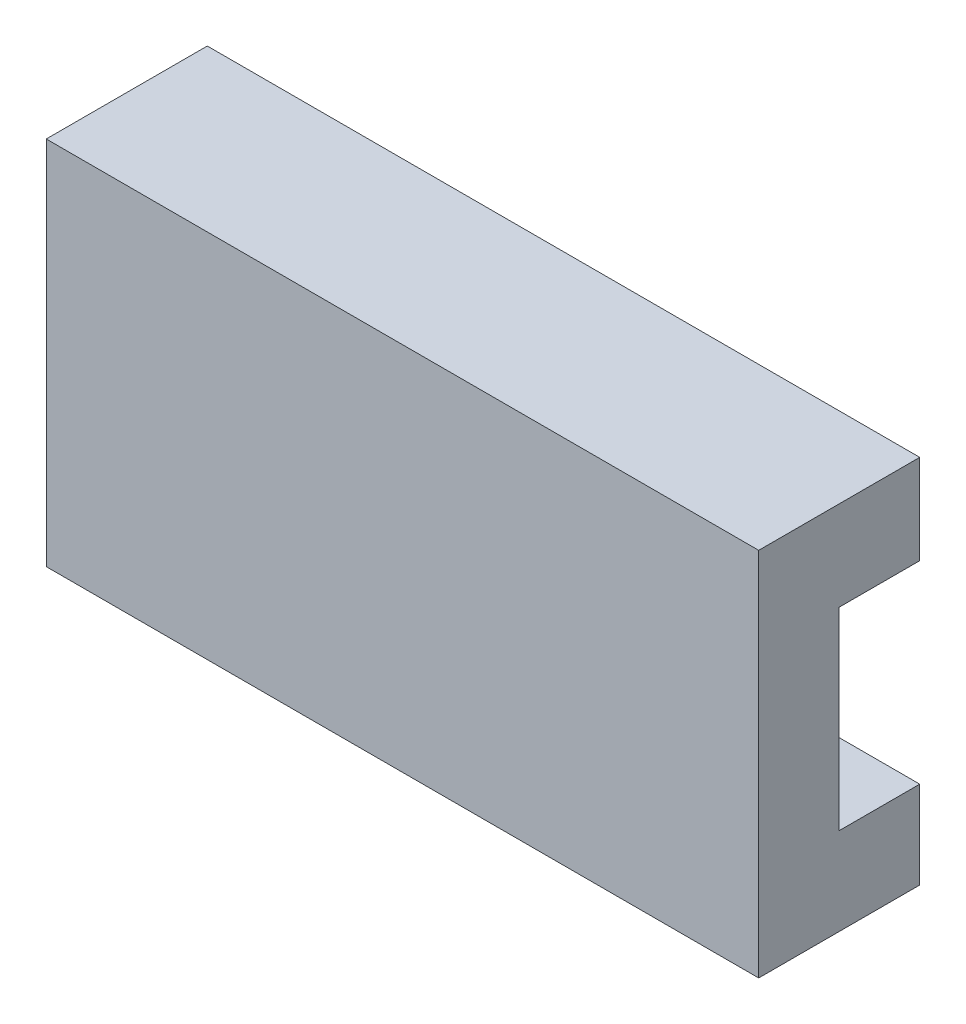
SolidWorks part; units mm, degrees
ref_plane "Front Plane" through (0, 0, 0) normal (0, 0, 1) x (1, 0, 0)
ref_plane "Top Plane" through (0, 0, 0) normal (0, 1, 0) x (1, 0, 0)
ref_plane "Right Plane" through (0, 0, 0) normal (1, 0, 0) x (0, 0, -1)
sketch "Sketch1" plane through (0, 0, 0) normal (0, 0, 1) x (1, 0, 0)
  line L0 (21.3, 8.5) -> (-21.3, 8.5) construction
  line L1 (-22.1208, 13.5) -> (22.1208, 13.5)
  line L2 (-22.1208, 13.5) -> (-22.1208, -9.5)
  line L3 (-22.1208, -9.5) -> (22.1208, -9.5)
  line L4 (22.1208, 13.5) -> (22.1208, -9.5)
  line L5 (-22.1208, 13.5) -> (22.1208, -9.5) construction
  line L6 (-22.1208, -9.5) -> (22.1208, 13.5) construction
  line L7 (-4.5, -4.5) -> (4.5, -4.5) construction
  point P0 (0, 2)
  dimension "D1" = 5
  dimension "D2" = 5
extrude "Boss-Extrude1" add sketch "Sketch1" along normal blind 10
sketch "Sketch2" plane through (0, 0, 0) normal (0, 0, 1) x (1, 0, 0)
  line L0 (22.1208, -9.5) -> (22.1208, 13.5) construction
  line L1 (-22.1208, -4.0745) -> (22.1208, -4.0745)
  line L2 (-22.1208, -4.0745) -> (-22.1208, 7.9415)
  line L3 (-22.1208, 7.9415) -> (22.1208, 7.9415)
  line L4 (22.1208, -4.0745) -> (22.1208, 7.9415)
  line L5 (-22.1208, -4.0745) -> (22.1208, 7.9415) construction
  line L6 (-22.1208, 7.9415) -> (22.1208, -4.0745) construction
  point P0 (0, 1.9335)
extrude "Cut-Extrude1" cut sketch "Sketch2" along normal blind 5
